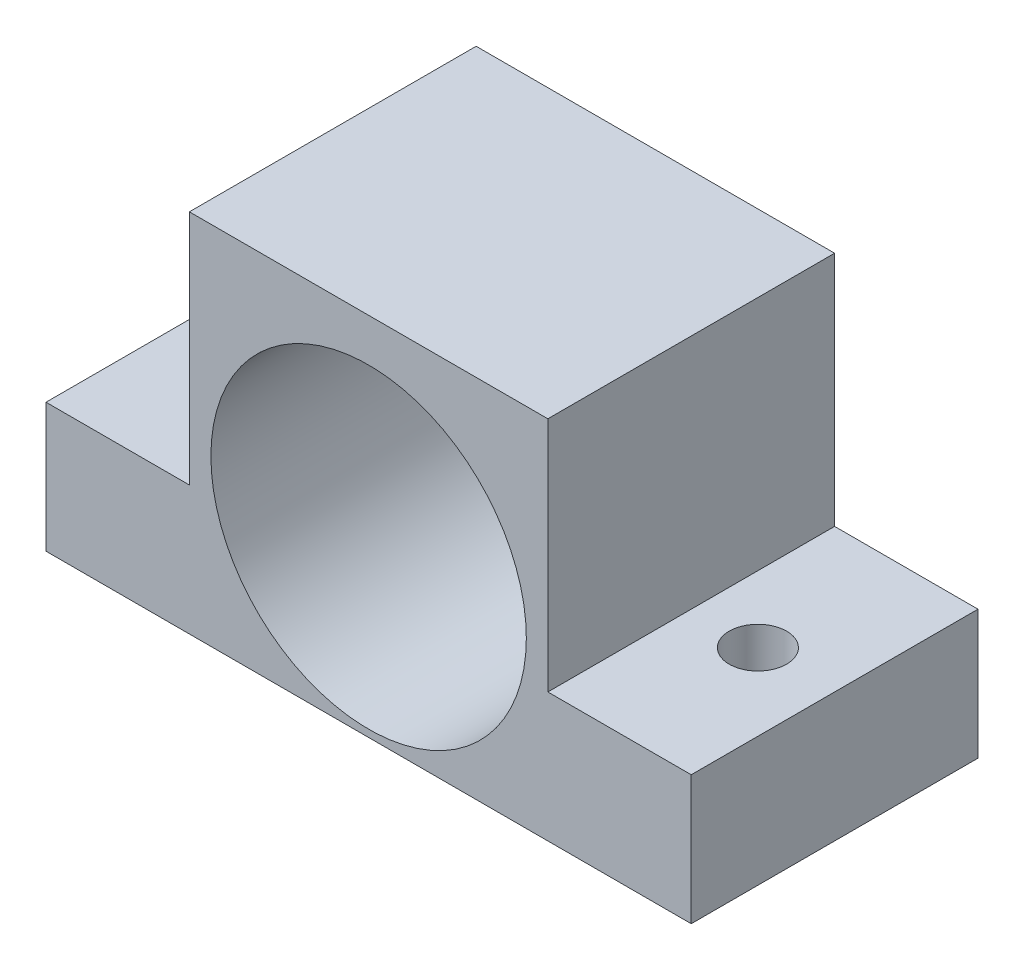
SolidWorks part; units mm, degrees
material "ABS"
ref_plane "Front Plane" through (0, 0, 0) normal (0, 0, 1) x (1, 0, 0)
ref_plane "Top Plane" through (0, 0, 0) normal (0, 1, 0) x (1, 0, 0)
ref_plane "Right Plane" through (0, 0, 0) normal (1, 0, 0) x (0, 0, -1)
sketch "Sketch1" plane through (0, 0, 0) normal (0, 0, 1) x (1, 0, 0)
  line L0 (185.6419, -17.5) -> (-64.3581, -17.5) construction
  line L1 (-11.4483, 8) -> (13.5517, 8)
  line L2 (-11.4483, 8) -> (-11.4483, -17.5)
  line L3 (-11.4483, -17.5) -> (13.5517, -17.5)
  line L4 (13.5517, 8) -> (13.5517, -17.5)
  line L5 (-11.4483, 8) -> (13.5517, -17.5) construction
  line L6 (-11.4483, -17.5) -> (13.5517, 8) construction
  line L7 (13.5517, -17.5) -> (23.5517, -17.5)
  line L8 (13.5517, -17.5) -> (13.5517, -8.5)
  line L9 (13.5517, -8.5) -> (23.5517, -8.5)
  line L10 (23.5517, -17.5) -> (23.5517, -8.5)
  line L11 (13.5517, -17.5) -> (23.5517, -8.5) construction
  line L12 (13.5517, -8.5) -> (23.5517, -17.5) construction
  line L13 (-11.4483, -17.5) -> (-21.4483, -17.5)
  line L14 (-11.4483, -17.5) -> (-11.4483, -8.5)
  line L15 (-11.4483, -8.5) -> (-21.4483, -8.5)
  line L16 (-21.4483, -17.5) -> (-21.4483, -8.5)
  line L17 (-11.4483, -17.5) -> (-21.4483, -8.5) construction
  line L18 (-11.4483, -8.5) -> (-21.4483, -17.5) construction
  circle A0 centre (1.0517, -6) radius 4.1
  circle A1 centre (1.0517, -6) radius 11
  circle A2 centre (1.0517, -6) radius 4 construction
  point P8 (1.0517, -6)
  point P14 (18.5517, -13)
  point P16 (-16.4483, -13)
  point P19 (0, 0)
  dimension "D4" = 8.2
  dimension "D5" = 22
  dimension "D1" = 14
  dimension "D3" = 25
  dimension "D6" = 10
  dimension "D7" = 9
  dimension "D8" = 10
  dimension "D9" = 9
  dimension "D10" = 12.5
extrude "Boss-Extrude1" add sketch "Sketch1" along normal blind 20 contours L4 L1 L2 L3 A1 | L16 L13 L2 L15 | L7 L10 L9 L4 region at (1.0517, 7.6429, 0) region at (-16.4483, -13, 0) region at (18.5517, -13, 0)
sketch "Sketch2" plane through (0, -8.5, 0) normal (0, 1, 0) x (1, 0, 0)
  line L1 (-11.4483, -20) -> (-21.4483, -20)
  line L4 (23.5517, -20) -> (23.5517, 0)
  circle A0 centre (-16.7988, -10) radius 2
  circle A1 centre (18.2012, -10) radius 2
  circle A2 centre (18.2012, -10) radius 2 construction
  circle A3 centre (-16.7988, -10) radius 2 construction
  dimension "D1" = 4
  dimension "D2" = 4
extrude "Cut-Extrude1" cut sketch "Sketch2" against normal blind 9 contours A0 | A0 | A0 | A0 | A1 region at (-16.7988, -8.5, 10)
